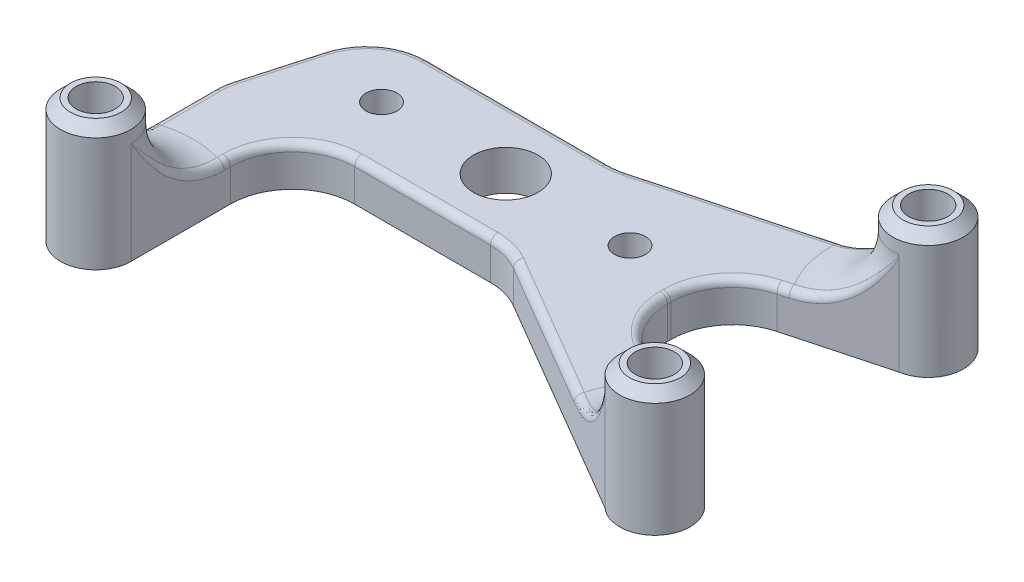
SolidWorks part; units mm, degrees
ref_plane "Front Plane" through (0, 0, 0) normal (0, 0, 1) x (1, 0, 0)
ref_plane "Top Plane" through (0, 0, 0) normal (0, 1, 0) x (1, 0, 0)
ref_plane "Right Plane" through (0, 0, 0) normal (1, 0, 0) x (0, 0, -1)
sketch "Sketch6" plane through (0, 0, 0) normal (0, 1, 0) x (1, 0, 0)
  line L1 (-19.05, -6.35) -> (19.05, -6.35)
  line L2 (-19.05, -6.35) -> (-19.05, 6.35)
  line L3 (-19.05, 6.35) -> (19.05, 6.35)
  line L4 (19.05, -6.35) -> (19.05, 6.35)
  line L5 (-19.05, -6.35) -> (19.05, 6.35) construction
  line L6 (-19.05, 6.35) -> (19.05, -6.35) construction
  point P0 (0, 0)
  dimension "D1" = 12.7
  dimension "D2" = 38.1
extrude "Boss-Extrude6" add sketch "Sketch6" along normal blind 3.175 separate body
sketch "Sketch4" plane through (0, 0, 0) normal (0, 1, 0) x (1, 0, 0)
  circle A0 centre (-19.05, -22.86) radius 3.6
  circle A1 centre (33.02, -17.78) radius 3.6
  circle A2 centre (33.02, 10.16) radius 3.6
  dimension "D1" = 7.2
  dimension "D2" = 7.2
  dimension "D3" = 7.2
  dimension "D4" = 52.07
  dimension "D5" = 5.08
  dimension "D6" = 27.94
  dimension "D7" = 10.16
  dimension "D8" = 33.02
extrude "Boss-Extrude5" add sketch "Sketch4" along normal blind 12.7
sketch "Sketch8" plane through (0, 0, 0) normal (0, 1, 0) x (1, 0, 0)
  line L2 (31.8384, 13.5606) -> (5.0632, 6.35)
  line L3 (19.05, 6.35) -> (-19.05, 6.35) construction
  line L4 (33.5862, 6.6048) -> (19.05, 2.6902)
  line L5 (19.05, -6.35) -> (19.05, 6.35) construction
  line L6 (19.05, 2.6902) -> (19.05, -6.35)
  line L7 (19.05, -6.35) -> (34.6277, -14.5589)
  line L8 (30.6114, -20.4556) -> (6.515, -6.35)
  line L9 (-19.05, -6.35) -> (19.05, -6.35) construction
  line L10 (6.515, -6.35) -> (-15.45, -6.35)
  line L11 (-15.45, -6.35) -> (-15.45, -22.86)
  line L12 (-22.65, -22.86) -> (-22.65, -6.35)
  line L13 (-22.65, -6.35) -> (-19.05, 6.35)
  line L14 (-19.05, 6.35) -> (5.0632, 6.35)
  circle A0 centre (33.02, 10.16) radius 3.6 construction
  arc A1 (33.5862, 6.6048) -> (31.8384, 13.5606) centre (33.02, 10.16) ccw
  circle A2 centre (33.02, -17.78) radius 3.6 construction
  arc A3 (34.6277, -14.5589) -> (30.6114, -20.4556) centre (33.02, -17.78) cw
  circle A4 centre (-19.05, -22.86) radius 3.6 construction
  arc A5 (-15.45, -22.86) -> (-22.65, -22.86) centre (-19.05, -22.86) cw
extrude "Boss-Extrude7" add sketch "Sketch8" along normal blind 4.064
fillet "Fillet1" radius 6.35 7 edges at (-15.45, 2.032, 6.35) (6.515, 2.032, 6.35) (19.05, 2.032, 6.35) (19.05, 2.032, -2.6902) (5.0632, 2.032, -6.35) (-22.65, 2.032, 6.35) (-19.05, 2.032, -6.35)
sketch "Sketch9" plane through (0, 4.064, 0) normal (0, 1, 0) x (1, 0, 0)
  circle A0 centre (-12.7, 0) radius 1.5875
  circle A1 centre (12.7, 0) radius 1.5875
  circle A2 centre (0, 0) radius 3.302
  dimension "D3" = 3.175
  dimension "D4" = 3.175
  dimension "D5" = 6.604
  dimension "D1" = 25.4
  dimension "D2" = 12.7
extrude "Cut-Extrude3" cut sketch "Sketch9" against normal through all
fillet "Fillet2" radius 6.35 3 edges at (-19.05, 4.064, 19.26) (30.0446, 4.064, 15.7534) (29.5285, 4.064, -9.2827)
sketch "Sketch10" plane through (0, 12.7, 0) normal (0, 1, 0) x (1, 0, 0)
  circle A0 centre (-19.05, -22.86) radius 2
  circle A1 centre (33.02, -17.78) radius 2
  circle A2 centre (33.02, 10.16) radius 2
  dimension "D1" = 4
  dimension "D2" = 4
  dimension "D3" = 4
extrude "Cut-Extrude4" cut sketch "Sketch10" against normal blind 5.7
chamfer "Chamfer1" distance 1.016 angle 45 3 edges at (33.02, 12.7, -6.56) (33.02, 12.7, 21.38) (-19.05, 12.7, 26.46)
fillet "Fillet3" radius 0.762 23 edges at (34.1822, 9.6509, 14.3242) (24.4655, 4.064, 9.2038) (33.042, 9.2814, -6.4582) (24.3677, 4.064, -4.1223) (20.3598, 4.064, -1.6865) (19.05, 4.064, 2.3472) (30.8667, 8.8079, -13.2989) (14.5002, 4.064, -8.8914) (5.0559, 4.064, -6.4048) (-22.65, 5.6615, 18.3911) (-22.65, 4.064, 10.4084) (-22.5895, 4.064, 6.3584) (-21.3842, 4.064, 1.8845) (-18.079, 4.064, -5.0655) (-15.45, 5.6615, 18.3911) (-15.45, 4.064, 13.142) (-13.5901, 4.064, 8.2099) (29.7882, 8.4666, 19.9737) (15.605, 4.064, 11.6711) (6.455, 4.064, 6.5713) (19.9631, 4.064, 5.7991) (-5.0133, 4.064, -6.35) (-2.1535, 4.064, 6.35)
sketch "Sketch11" plane through (0, 7, 0) normal (0, 1, 0) x (1, 0, 0)
  circle A0 centre (-19.05, -22.86) radius 1.5875
  circle A1 centre (33.02, -17.78) radius 1.5875
  circle A2 centre (33.02, 10.16) radius 1.5875
  dimension "D1" = 3.175
  dimension "D2" = 3.175
  dimension "D3" = 3.175
extrude "Cut-Extrude5" cut sketch "Sketch11" against normal through all
